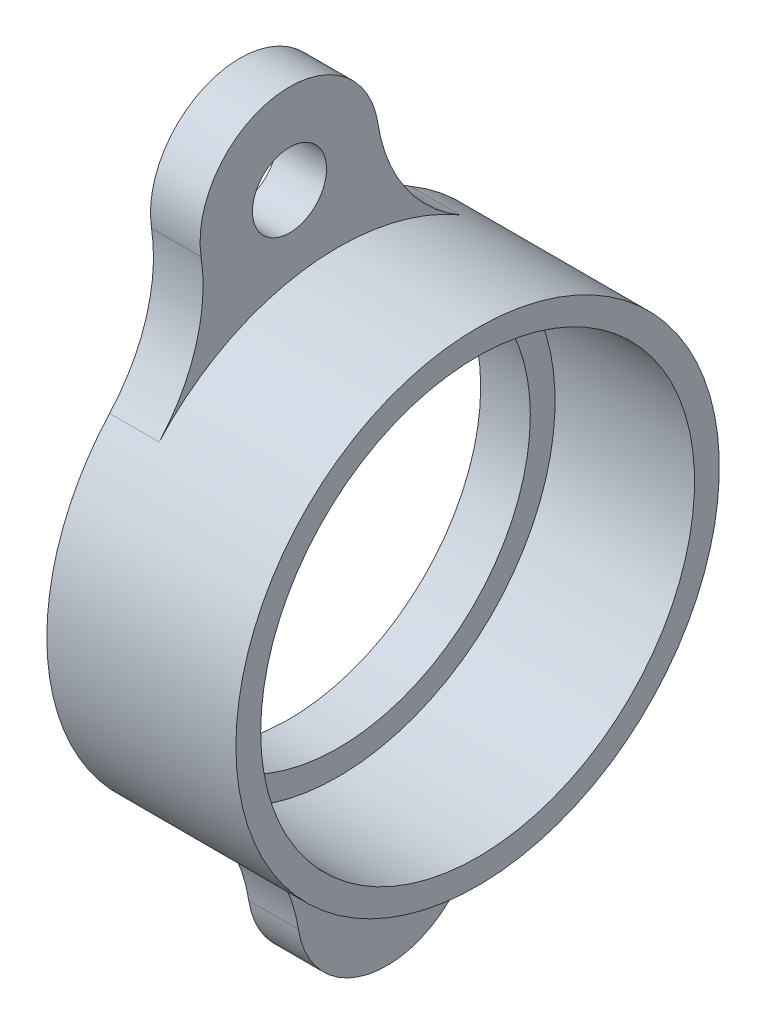
SolidWorks part; units mm, degrees
material "6061-T6 (SS)"
ref_plane "Front Plane" through (0, 0, 0) normal (0, 0, 1) x (1, 0, 0)
ref_plane "Top Plane" through (0, 0, 0) normal (0, 1, 0) x (1, 0, 0)
ref_plane "Right Plane" through (0, 0, 0) normal (1, 0, 0) x (0, 0, -1)
sketch "Sketch1" plane through (0, 0, 0) normal (0, 0, 1) x (1, 0, 0)
  line L0 (23.3719, 12.3825) -> (30.5156, 12.3825)
  line L1 (30.5156, 12.3825) -> (30.5156, 11.1125)
  line L2 (30.5156, 11.1125) -> (23.3719, 11.1125)
  line L4 (23.3719, 11.1125) -> (23.3719, 12.3825)
  line L5 (0, 0) -> (40.0174, 0) construction
  dimension "D1" = 22.225
  dimension "D2" = 7.1437
revolve "Revolve1" add sketch "Sketch1" angle 360 about L5
sketch "Sketch2" plane through (23.3719, 0, 0) normal (1, 0, 0) x (0, 0, -1)
  line L0 (0, 0) -> (-2.4917, 16.1603) construction
  line L1 (-7.0209, 15.4619) -> (2.0375, 16.8586) construction
  line L2 (-10.9827, -1.6934) -> (10.9827, 1.6934) construction
  line L4 (-4.1515, 11.8887) -> (0.3777, 12.5871) construction
  line L5 (0.3777, 12.5871) -> (2.0375, 16.8586) construction
  line L6 (2.0375, 16.8586) -> (-0.8319, 20.4319) construction
  line L7 (-0.8319, 20.4319) -> (-5.3611, 19.7335) construction
  line L8 (-5.3611, 19.7335) -> (-7.0209, 15.4619) construction
  line L9 (-7.0209, 15.4619) -> (-4.1515, 11.8887) construction
  arc A0 (-9.1674, 8.3237) -> (-6.2344, -10.6985) centre (0, 0) ccw
  circle A1 centre (0, 0) radius 12.3825 construction
  arc A7 (2.0375, 16.8586) -> (-7.0209, 15.4619) centre (-2.4917, 16.1603) ccw
  arc A8 (-9.1674, 8.3237) -> (-7.0209, 15.4619) centre (-15.5764, 14.1428) ccw
  arc A9 (2.0375, 16.8586) -> (6.2344, 10.6985) centre (10.5929, 18.1778) ccw
  circle A10 centre (0, 0) radius 9.8425
  circle A11 centre (0, 0) radius 11.1125 construction
  arc A16 (9.1674, -8.3237) -> (6.2344, 10.6985) centre (0, 0) ccw
  circle A17 centre (-2.4917, 16.1603) radius 3.9688 construction
  circle A18 centre (-2.4917, 16.1603) radius 2.1526 construction
  circle A19 centre (-2.4917, 16.1603) radius 2.1526 construction
  circle A20 centre (0, 0) radius 11.1125 construction
  arc A21 (7.0209, -15.4619) -> (9.1674, -8.3237) centre (15.5764, -14.1428) cw
  arc A22 (-6.2344, -10.6985) -> (-2.0375, -16.8586) centre (-10.5929, -18.1778) cw
  arc A23 (7.0209, -15.4619) -> (-2.0375, -16.8586) centre (2.4917, -16.1603) cw
  dimension "D1" = 1.27
  dimension "D3" = 7.9375
extrude "Boss-Extrude1" add sketch "Sketch2" against normal blind 2.54
hole_wizard "#6 Clearance Hole1" positions "Sketch3" profile "Sketch5" hole size "#6" standard "ANSI Inch" end condition up to next
sketch "Sketch3" plane through (20.8319, 0, 0) normal (-1, 0, 0) x (0, 0, 1)
  arc A0 (-7.0209, -15.4619) -> (2.0375, -16.8586) centre (-2.4917, -16.1603) ccw construction
  point P0 (2.4917, 16.1603)
  point P3 (-2.4917, -16.1603)
sketch "Sketch5" plane through (20.8319, 16.1603, 2.4917) normal (0, 1, 0) x (0, 0, 1)
  line L0 (0, 0) -> (0, 2.54)
  line L1 (0, 2.54) -> (1.8986, 2.54)
  line L2 (1.8986, 2.54) -> (1.8986, 0)
  line L5 (1.8986, 0) -> (0, 0)
  line L11 (0, -6.35) -> (0, 107.95) construction
  dimension "Thru Hole Dia." = 3.7973
  dimension "Thru Hole Depth" = 2.54
